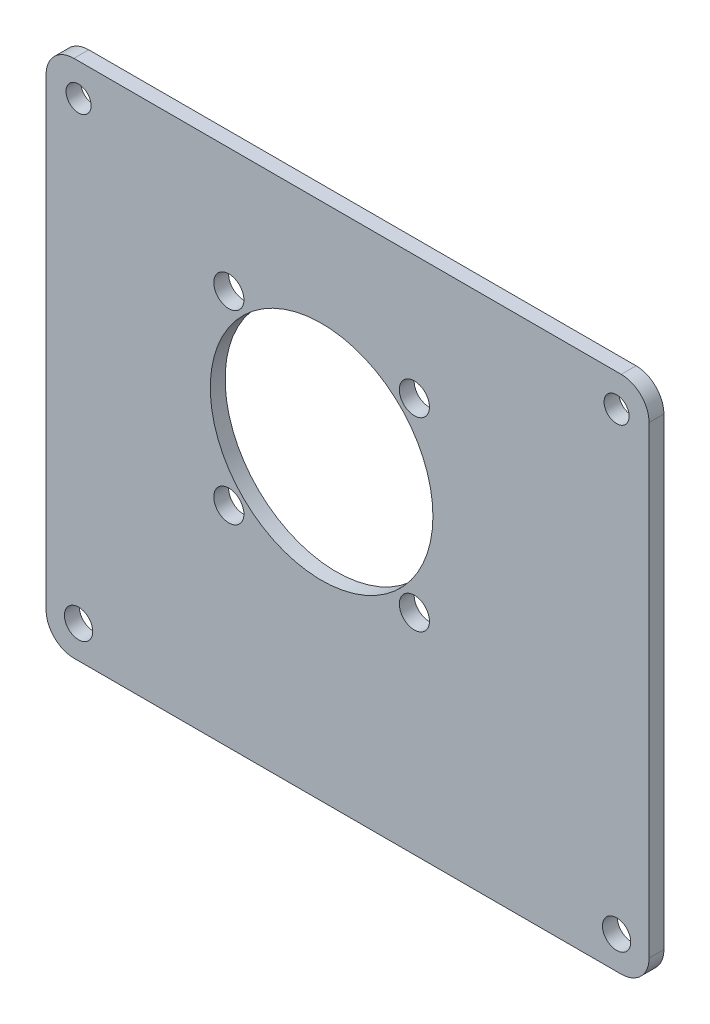
SolidWorks part; units mm, degrees
ref_plane "Front Plane" through (0, 0, 0) normal (0, 0, 1) x (1, 0, 0)
ref_plane "Top Plane" through (0, 0, 0) normal (0, 1, 0) x (1, 0, 0)
ref_plane "Right Plane" through (0, 0, 0) normal (1, 0, 0) x (0, 0, -1)
sketch "Sketch1" plane through (0, 0, 0) normal (0, 0, 1) x (1, 0, 0)
  line L0 (22.5, 25) -> (22.5, -25)
  line L1 (19, 24.5) -> (19.5, 25) construction
  line L2 (39.5, 28) -> (-39.5, 28) construction
  line L4 (42.5, -25) -> (42.5, 25)
  line L5 (39.5, 28) -> (-39.5, 28)
  line L6 (-42.5, 25) -> (-42.5, -25)
  line L7 (-39.5, -28) -> (39.5, -28)
  line L9 (19.5, 28) -> (-39.5, 28)
  line L10 (-42.5, 25) -> (-42.5, -25)
  line L11 (-39.5, -28) -> (19.5, -28)
  arc A0 (22.5, 25) -> (19.5, 28) centre (19.5, 25) ccw
  arc A1 (22.5, -25) -> (19.5, -28) centre (19.5, -25) cw
  circle A2 centre (19, 24.5) radius 1.35 construction
  circle A3 centre (-39, 24.5) radius 1.35 construction
  arc A4 (42.5, 25) -> (39.5, 28) centre (39.5, 25) ccw
  arc A5 (-39.5, 28) -> (-42.5, 25) centre (-39.5, 25) ccw
  arc A6 (-42.5, -25) -> (-39.5, -28) centre (-39.5, -25) ccw
  arc A7 (39.5, -28) -> (42.5, -25) centre (39.5, -25) ccw
  arc A9 (-39.5, 28) -> (-42.5, 25) centre (-39.5, 25) ccw
  arc A10 (-42.5, -25) -> (-39.5, -28) centre (-39.5, -25) ccw
  circle A11 centre (-39, -24.5) radius 1.524 construction
  circle A12 centre (19, -24.5) radius 1.524 construction
  circle A13 centre (-39, 24.5) radius 1.35
  circle A14 centre (-39, -24.5) radius 1.524
  circle A15 centre (19, -24.5) radius 1.524
  circle A16 centre (19, 24.5) radius 1.35
  point P18 (19, 24.5)
  dimension "D2" = 45
  dimension "D1" = 0
extrude "Boss-Extrude1" add sketch "Sketch1" along normal blind 1.6
sketch "Sketch2" plane through (0, 0, 1.6) normal (0, 0, 1) x (1, 0, 0)
  circle A0 centre (-2.7999, 14.61) radius 1.625
  circle A1 centre (-22.7999, 14.61) radius 1.625
  circle A2 centre (-22.7999, -5.39) radius 1.625
  circle A3 centre (-2.7999, -5.39) radius 1.625
  circle A4 centre (-12.7999, 4.61) radius 12
  dimension "D1" = 3.25
  dimension "D2" = 24
extrude "Cut-Extrude1" cut sketch "Sketch2" against normal through all
